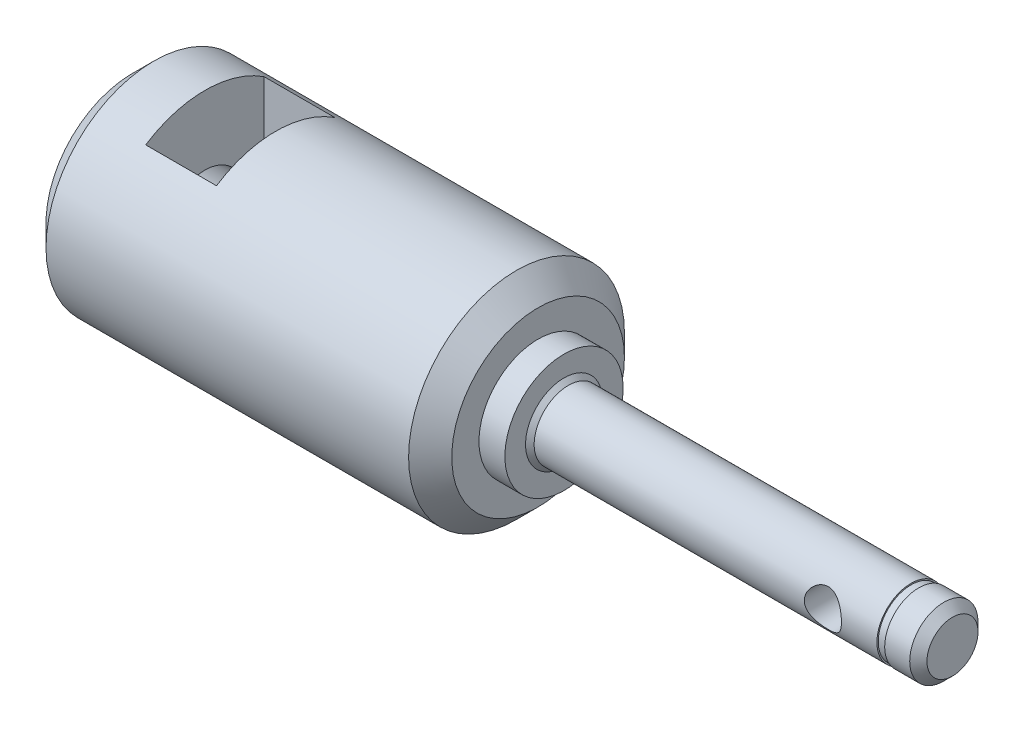
SolidWorks part; units mm, degrees
material "PLA"
ref_plane "Front Plane" through (0, 0, 0) normal (0, 0, 1) x (1, 0, 0)
ref_plane "Top Plane" through (0, 0, 0) normal (0, 1, 0) x (1, 0, 0)
ref_plane "Right Plane" through (0, 0, 0) normal (1, 0, 0) x (0, 0, -1)
sketch "Sketch1" plane through (0, 0, 0) normal (1, 0, 0) x (0, 0, -1)
  circle A1 centre (0, 0) radius 12.5
  dimension "D2" = 25
extrude "Boss-Extrude1" add sketch "Sketch1" against normal blind 50
sketch "Sketch6" plane through (0, 0, 0) normal (1, 0, 0) x (0, 0, -1)
  circle A0 centre (0, 0) radius 6.85
  circle A1 centre (0, 0) radius 12.5
  dimension "D1" = 13.7
  dimension "D2" = 25
extrude "Cut-Extrude4" cut sketch "Sketch6" against normal blind 3
sketch "Sketch7" plane through (0, 0, 0) normal (1, 0, 0) x (0, 0, -1)
  circle A0 centre (0, 0) radius 3.955
  dimension "D1" = 7.91
extrude "Boss-Extrude3" add sketch "Sketch7" along normal blind 45
ref_axis "Axis2" through (-50, 0, 0) along (1, 0, 0)
sketch "Sketch8" plane through (0, 0, 0) normal (0, 0, 1) x (1, 0, 0)
  line L0 (45, 3.955) -> (45, -3.955) construction
  line L1 (45, -3.955) -> (45, 0) construction
  line L2 (45, 0) -> (33.94, 0) construction
  circle A0 centre (33.94, 0) radius 2.15
  dimension "D2" = 4.3
  dimension "D1" = 11.06
extrude "Cut-Extrude5" cut sketch "Sketch8" against normal through all and the other way through all
ref_plane "Plane2" through (40.2, 0, 0) normal (1, 0, 0) x (0, 0, -1)
sketch "Sketch9" plane through (40.2, 0, 0) normal (1, 0, 0) x (0, 0, -1)
  circle A0 centre (0, 0) radius 3.97
  circle A1 centre (0, 0) radius 3.8
  dimension "D1" = 7.94
  dimension "D2" = 7.6
extrude "Cut-Extrude6" cut sketch "Sketch9" along normal blind 0.9
sketch "Sketch10" plane through (-50, 0, 0) normal (-1, 0, 0) x (0, 0, 1)
  circle A0 centre (0, 0) radius 4
  dimension "D1" = 8
extrude "Cut-Extrude7" cut sketch "Sketch10" against normal blind 20
chamfer "Chamfer2" distance 2.5 angle 45 1 edges at (-50, 0, -12.5)
chamfer "Chamfer3" distance 2.5 angle 45 1 edges at (-3, 0, -12.5)
chamfer "Chamfer4" distance 1 angle 45 1 edges at (45, 0, -3.955)
sketch "Sketch2" plane through (-50, 0, 0) normal (-1, 0, 0) x (0, 0, 1)
  circle A0 centre (0, 0) radius 8.9631
extrude "Boss-Extrude2" add sketch "Sketch2" against normal blind 35
sketch "Sketch3" plane through (-50, 0, 0) normal (-1, 0, 0) x (0, 0, 1)
  line L1 (-6, -6) -> (6, -6)
  line L2 (-6, -6) -> (-6, 6)
  line L3 (-6, 6) -> (6, 6)
  line L4 (6, -6) -> (6, 6)
  line L5 (-6, -6) -> (6, 6) construction
  line L6 (-6, 6) -> (6, -6) construction
  point P0 (0, 0)
  dimension "D1" = 12
  dimension "D2" = 12
extrude "Cut-Extrude1" [suppressed] cut sketch "Sketch3" against normal blind 30
sketch "Sketch4" plane through (0, 0, 0) normal (0, 0, 1) x (1, 0, 0)
  line L0 (-50, 0) -> (0, 0) construction
  line L1 (-50, 12.5) -> (-50, -12.5) construction
  line L3 (-100, 12.5) -> (-100, -12.5) construction
  line L4 (-5.5, 12.5) -> (-47.5, 12.5) construction
  line L5 (-47.5, -12.5) -> (-5.5, -12.5) construction
  line L6 (0, -12.5) -> (0, 12.5) construction
  circle A0 centre (-35, 0) radius 4.05
  circle A1 centre (-75, 0) radius 4.05
  circle A2 centre (-25, 0) radius 4.05
  dimension "D1" = 8.1
  dimension "D2" = 8.1
  dimension "D3" = 8.1
  dimension "D4" = 15
  dimension "D5" = 100
  dimension "D6" = 25
  dimension "D7" = 75
extrude "Cut-Extrude2" [suppressed] cut sketch "Sketch4" against normal blind 30 and the other way blind 30
ref_axis "Axis1" through (-47.5, 0, 0) along (1, 0, 0)
chamfer "Chamfer1" [suppressed] distance 2 angle 45
ref_plane "Plane1" through (0, 0, 12.5) normal (0, 0, 1) x (1, 0, 0)
sketch "Sketch5" [suppressed] plane through (0, 0, 12.5) normal (0, 0, 1) x (1, 0, 0)
  circle A0 centre (-135, 0) radius 7.5
  circle A1 centre (-75, 0) radius 7.5
  circle A2 centre (-25, 0) radius 7.5
  dimension "D1" = 15
extrude "Cut-Extrude3" [suppressed] cut sketch "Sketch5" against normal blind 1
mirror "Mirror1" [suppressed] about plane through (0, 0, 0) normal (0, 0, 1)
sketch "Sketch12" plane through (-50, 0, 0) normal (-1, 0, 0) x (0, 0, 1)
  circle A0 centre (0, 0) radius 4.5
  circle A1 centre (0, 0) radius 9.5
  dimension "D1" = 19
  dimension "D2" = 9
extrude "Boss-Extrude4" add sketch "Sketch12" against normal blind 9
sketch "Sketch11" plane through (0, 0, 0) normal (0, 1, 0) x (1, 0, 0)
  line L0 (-50, 0) -> (-37.5, 0) construction
  line L1 (-50, 12.5) -> (-50, -12.5) construction
  line L2 (-50, 0) -> (-3, 0) construction
  line L4 (-41.6, -6.85) -> (-33.4, -6.85)
  line L5 (-41.6, -6.85) -> (-41.6, 6.85)
  line L6 (-41.6, 6.85) -> (-33.4, 6.85)
  line L7 (-33.4, -6.85) -> (-33.4, 6.85)
  line L8 (-41.6, -6.85) -> (-33.4, 6.85) construction
  line L9 (-41.6, 6.85) -> (-33.4, -6.85) construction
  dimension "D1" = 13.7
  dimension "D2" = 12.5
  dimension "D3" = 8.2
extrude "Cut-Extrude8" cut sketch "Sketch11" against normal through all and the other way through all
sketch "Sketch13" plane through (-50, 0, 0) normal (-1, 0, 0) x (0, 0, 1)
  circle A0 centre (0, 0) radius 4.5
  dimension "D1" = 9
extrude "Cut-Extrude9" cut sketch "Sketch13" against normal blind 17
chamfer "Chamfer5" distance 0.5 angle 45 1 edges at (0, 0, -3.955)
